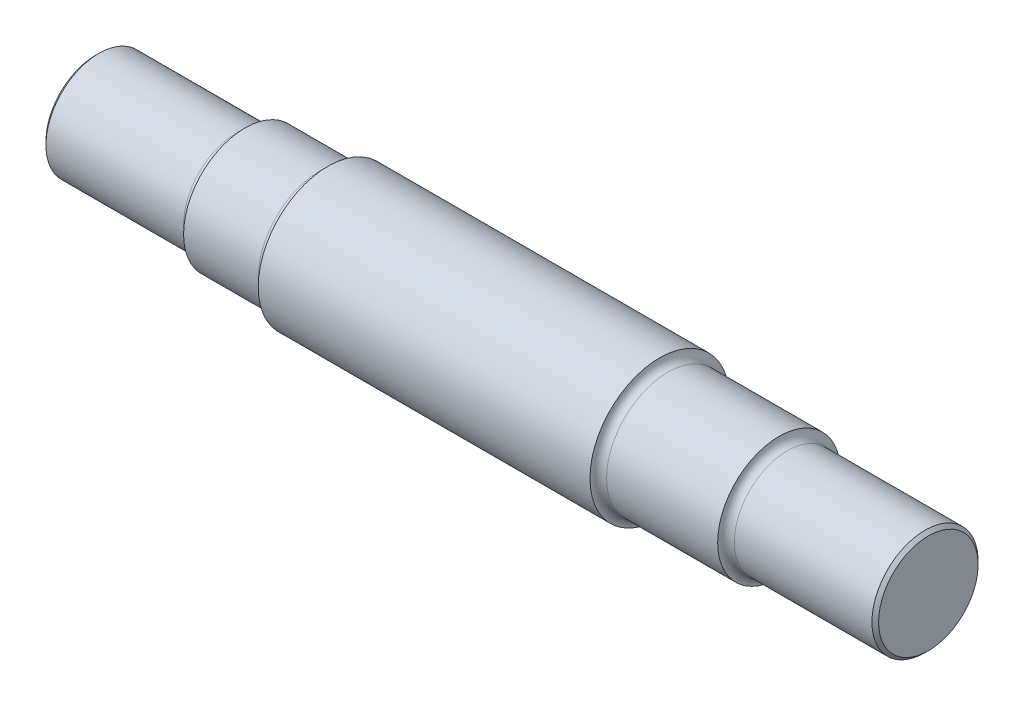
SolidWorks part; units mm, degrees
ref_plane "Front Plane" through (0, 0, 0) normal (0, 0, 1) x (1, 0, 0)
ref_plane "Top Plane" through (0, 0, 0) normal (0, 1, 0) x (1, 0, 0)
ref_plane "Right Plane" through (0, 0, 0) normal (1, 0, 0) x (0, 0, -1)
sketch "Sketch1" plane through (0, 0, 0) normal (0, 0, 1) x (1, 0, 0)
  line L0 (0, 0) -> (251, 0)
  line L1 (0, 0) -> (0, 16)
  line L2 (0, 16) -> (45, 16)
  line L3 (45, 16) -> (45, 18.5)
  line L4 (45, 18.5) -> (70, 18.5)
  line L5 (70, 18.5) -> (70, 21)
  line L6 (70, 21) -> (170, 21)
  line L7 (170, 21) -> (170, 18.5)
  line L8 (170, 18.5) -> (206, 18.5)
  line L9 (206, 18.5) -> (206, 16)
  line L10 (206, 16) -> (251, 16)
  line L11 (251, 16) -> (251, 0)
  point P11 (22.5, 16)
  point P14 (57.5, 18.5)
  point P15 (188, 18.5)
  point P16 (228.5, 16)
  dimension "D1" = 45
  dimension "D2" = 45
  dimension "D3" = 25
  dimension "D4" = 36
  dimension "D5" = 100
  dimension "D6" = 16
  dimension "D7" = 2.5
  dimension "D8" = 2.5
revolve "Revolve1" add sketch "Sketch1" angle 360 about L0
fillet "Fillet1" radius 2.5 4 edges at (206, 0, 16) (170, 0, 18.5) (70, 0, 18.5) (45, 0, 16)
chamfer "Chamfer1" distance 1 angle 45 2 edges at (251, 0, 16) (0, 0, 16)
